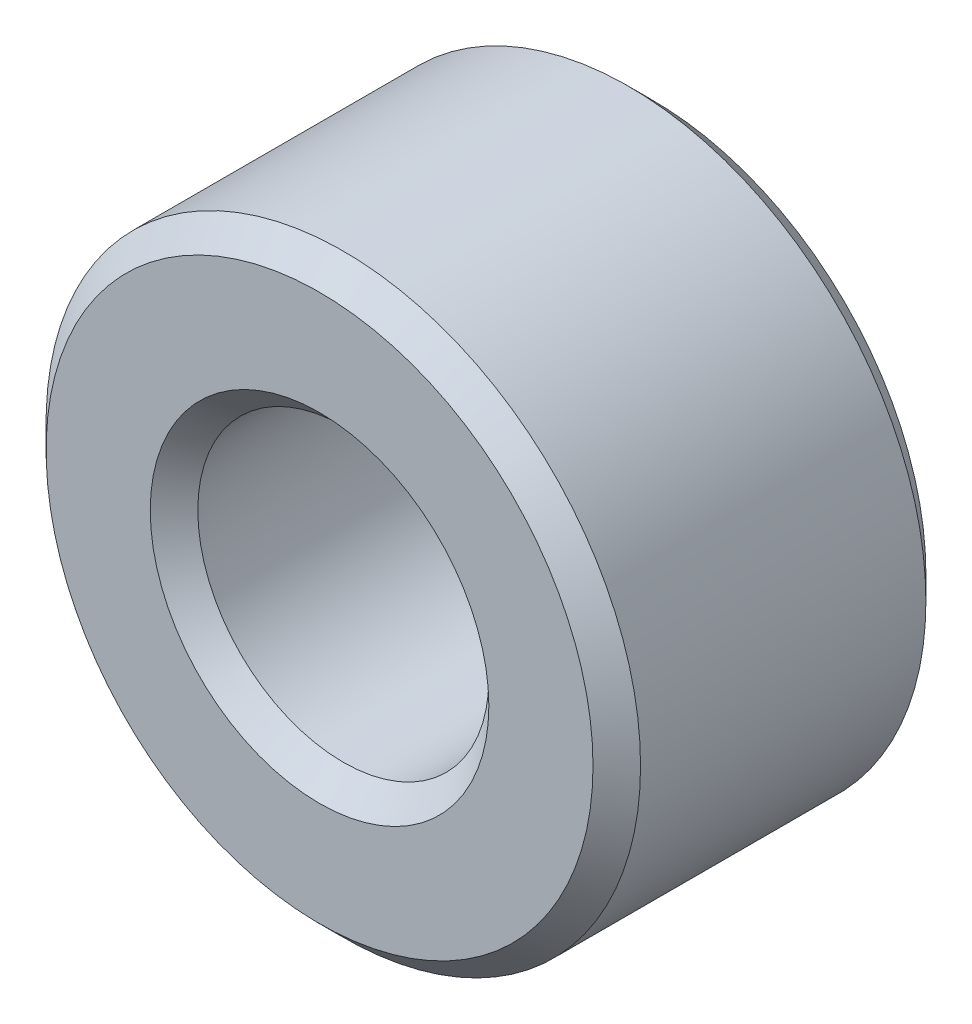
SolidWorks part; units mm, degrees
ref_plane "Front Plane" through (0, 0, 0) normal (1, 0, 0) x (0, 1, 0)
ref_plane "Top Plane" through (0, 0, 0) normal (0, 0, 1) x (0, 1, 0)
ref_plane "Right Plane" through (0, 0, 0) normal (0, 1, 0) x (-1, 0, 0)
sketch "Sketch2" plane through (0, 0, 0) normal (0, 0, 1) x (0, 1, 0)
  circle A0 centre (0, 0) radius 7.9375
  circle A1 centre (0, 0) radius 1.7082
  circle A2 centre (0, 0) radius 3.8862
extrude "Boss-Extrude1" add sketch "Sketch2" along normal blind 6.35 contours A0 A1 | A1 | A1 region at (0, -7.713, 0) region at (0, 0, 0)
delete or keep bodies "Body-Delete/Keep 1" type delete bodies bodies 104
extrude "Boss-Extrude3" add sketch "Sketch2<6>" against normal blind 2.54 contours A1 | A0
sketch "Sketch2<6>" plane through (0, 0, 0) normal (0, 0, 1) x (0, 1, 0) same geometry as "Sketch2"
chamfer "Chamfer2" distance 1.27 angle 50 1 edges at (1.7082, 0, -2.54) first distance on face at (1.7082, 0, -2.54)
chamfer "Chamfer3" distance 0.635 3 edges at (3.8862, 0, 6.35) (7.9375, 0, 6.35) (7.9375, 0, -2.54)
